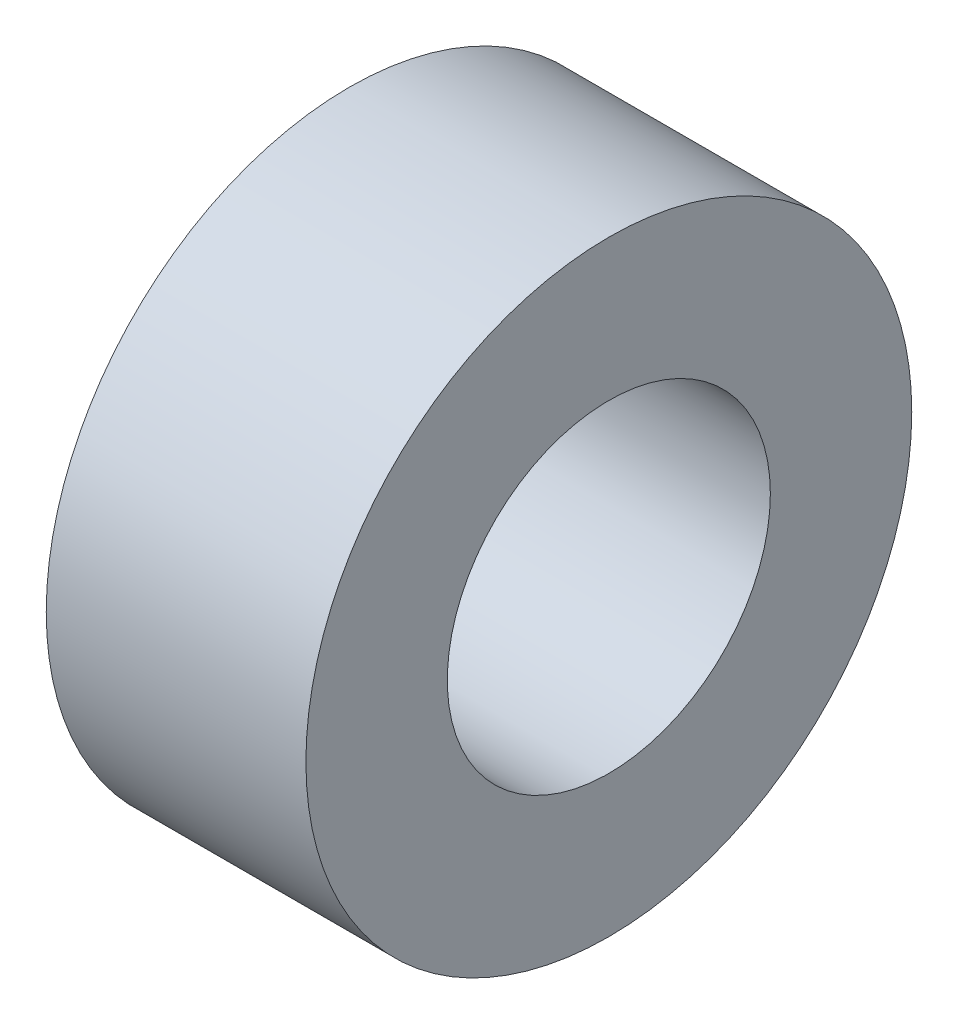
SolidWorks part; units mm, degrees
ref_plane "Front Plane" through (0, 0, 0) normal (0, 0, 1) x (1, 0, 0)
ref_plane "Top Plane" through (0, 0, 0) normal (0, 1, 0) x (1, 0, 0)
ref_plane "Right Plane" through (0, 0, 0) normal (1, 0, 0) x (0, 0, -1)
sketch "Sketch1" plane through (0, 0, 0) normal (1, 0, 0) x (0, 0, -1)
  circle A0 centre (0, 0) radius 7
  circle A1 centre (0, 0) radius 3.7326
extrude "Boss-Extrude1" add sketch "Sketch1" along normal blind 6
